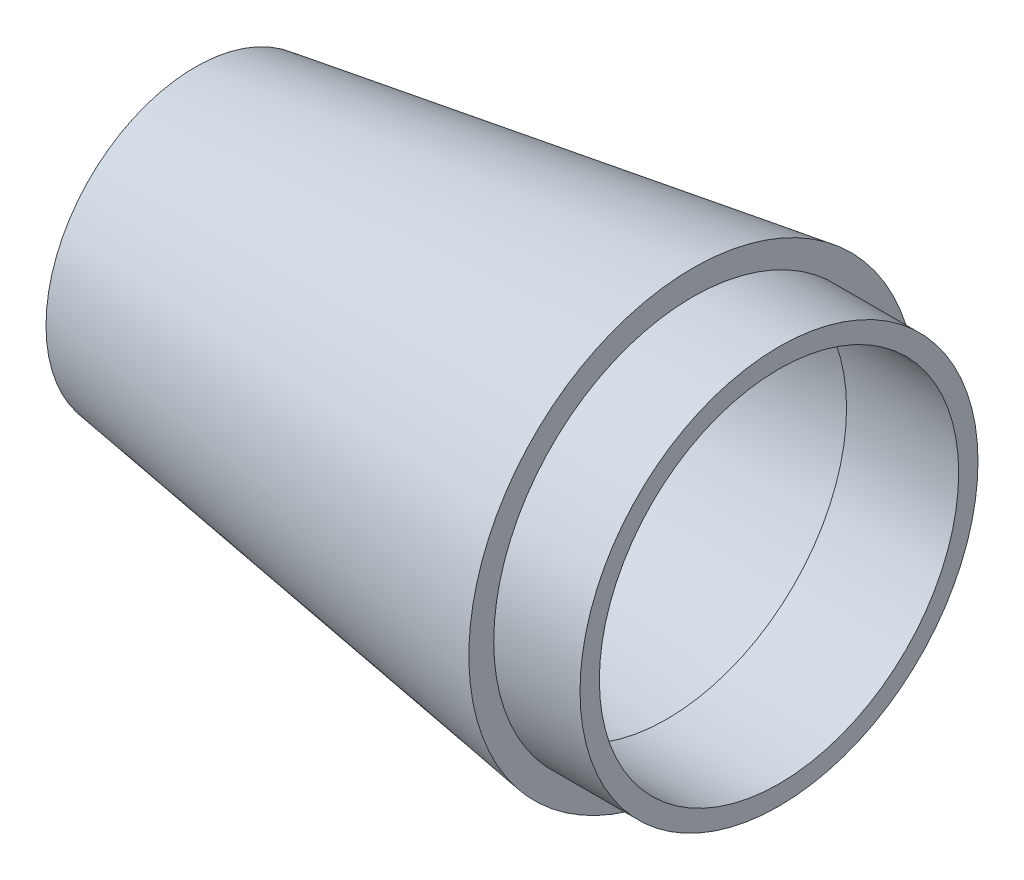
SolidWorks part; units mm, degrees
ref_plane "Front Plane" through (0, 0, 0) normal (0, 0, 1) x (1, 0, 0)
ref_plane "Top Plane" through (0, 0, 0) normal (0, 1, 0) x (1, 0, 0)
ref_plane "Right Plane" through (0, 0, 0) normal (1, 0, 0) x (0, 0, -1)
sketch "Sketch1" plane through (0, 0, 0) normal (0, 0, 1) x (1, 0, 0)
  line L0 (-12.065, 7.62) -> (-12.065, 6.35)
  line L1 (44.7264, 0) -> (-69.8413, 0) construction
  line L2 (13.335, 11.43) -> (13.335, 10.16)
  line L3 (-12.065, 0) -> (14.2126, 0) construction
  line L4 (-0.9413, 9.2885) -> (-0.9413, 0)
  line L5 (13.335, 11.43) -> (-12.065, 7.62)
  line L6 (-12.065, 6.35) -> (13.335, 10.16)
  line L7 (-0.9413, 0) -> (0.635, 0)
  line L8 (0.635, 0) -> (0.635, 9.525)
  line L9 (0.635, 9.525) -> (-0.9413, 9.2885)
  line L11 (17.7092, 9.1735) -> (12.0168, 9.1735)
  line L12 (12.0168, 9.1735) -> (12.0168, 9.9623)
  line L13 (12.0168, 9.9623) -> (13.335, 10.16)
  line L14 (13.335, 10.16) -> (17.7414, 10.16)
  line L15 (17.7414, 9.1735) -> (17.7092, 9.1735)
  line L16 (17.7414, 10.16) -> (17.7414, 9.1735)
  dimension "D1" = 25.4
  dimension "D2" = 1.27
  dimension "D3" = 7.62
  dimension "D4" = 11.43
  dimension "D5" = 1.27
revolve "Revolve4" add sketch "Sketch1" angle 360 about L1 region at (-6.5032, 7.8193, 0) region at (-0.1494, 4.0687, 0) region at (6.985, 9.8425, 0)
sketch "Sketch2" plane through (0.635, 0, 0) normal (1, 0, 0) x (0, 0, -1)
  line L3 (-0.3129, 0) -> (0.3129, 0)
  line L4 (-0.3129, 0) -> (-0.3129, 1.0082)
  line L5 (-0.3129, 1.0082) -> (0.3129, 1.0082)
  line L6 (0.3129, 0) -> (0.3129, 1.0082)
  line L9 (-0.3129, 1.0082) -> (0.3129, 1.0082)
  line L10 (-0.3129, 1.0082) -> (-0.3129, 0.7863)
  line L11 (-0.3129, 0.7863) -> (0.3129, 0.7863)
  line L12 (0.3129, 1.0082) -> (0.3129, 0.7863)
  point P3 (0, 0)
  point P8 (0, 0)
